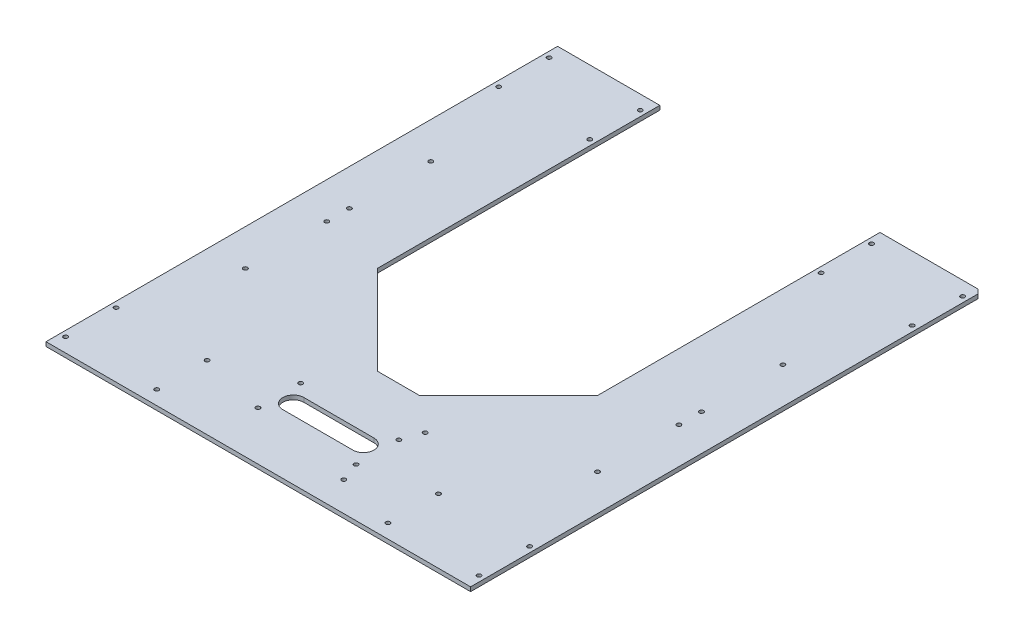
SolidWorks part; units mm, degrees
material "3.3315 (EN-AW 5005)"
ref_plane "Front Plane" through (0, 0, 0) normal (0, 0, 1) x (1, 0, 0)
ref_plane "Top Plane" through (0, 0, 0) normal (0, 1, 0) x (1, 0, 0)
ref_plane "Right Plane" through (0, 0, 0) normal (1, 0, 0) x (0, 0, -1)
sketch "Sketch1" plane through (0, 0, 0) normal (0, 1, 0) x (1, 0, 0)
  line L0 (0, 0) -> (0, -365)
  line L1 (0, -365) -> (302.93, -365)
  line L2 (302.93, -365) -> (302.93, 0)
  line L3 (302.93, 0) -> (230, 0)
  line L4 (230, 0) -> (230, -265)
  line L5 (230, -265) -> (72.93, -265)
  line L6 (72.93, -265) -> (72.93, 0)
  line L7 (72.93, 0) -> (0, 0)
  line L8 (72.93, -201.465) -> (136.465, -265)
  line L9 (166.465, -265) -> (230, -201.465)
  line L10 (151.465, -265) -> (151.465, -365) construction
  line L11 (126.465, -315) -> (176.465, -315) construction
  line L12 (126.465, -307.5) -> (176.465, -307.5)
  line L13 (126.465, -322.5) -> (176.465, -322.5)
  line L14 (0, -182.5) -> (72.93, -182.5) construction
  line L15 (116.465, -299.75) -> (186.465, -330.25) construction
  line L16 (191.465, -285.965) -> (191.465, -344.035) construction
  arc A0 (126.465, -307.5) -> (126.465, -322.5) centre (126.465, -315) ccw
  arc A1 (176.465, -322.5) -> (176.465, -307.5) centre (176.465, -315) ccw
  circle A2 centre (3.97, -10) radius 1.5
  circle A3 centre (3.97, -46.01) radius 1.5
  circle A4 centre (68.96, -10) radius 1.5
  circle A5 centre (68.96, -46.01) radius 1.5
  circle A6 centre (68.96, -318.99) radius 1.5
  circle A7 centre (68.96, -355) radius 1.5
  circle A8 centre (3.97, -318.99) radius 1.5
  circle A9 centre (3.97, -355) radius 1.5
  circle A10 centre (298.96, -355) radius 1.5
  circle A11 centre (298.96, -318.99) radius 1.5
  circle A12 centre (233.97, -355) radius 1.5
  circle A13 centre (233.97, -318.99) radius 1.5
  circle A14 centre (233.97, -46.01) radius 1.5
  circle A15 centre (233.97, -10) radius 1.5
  circle A16 centre (298.96, -46.01) radius 1.5
  circle A17 centre (298.96, -10) radius 1.5
  circle A18 centre (116.465, -330.25) radius 1.5
  circle A19 centre (116.465, -299.75) radius 1.5
  circle A20 centre (186.465, -299.75) radius 1.5
  circle A21 centre (186.465, -330.25) radius 1.5
  circle A22 centre (25.86, -116.36) radius 1.5
  circle A23 centre (25.86, -174.43) radius 1.5
  circle A24 centre (25.86, -190.57) radius 1.5
  circle A25 centre (25.86, -248.64) radius 1.5
  circle A26 centre (277.07, -248.64) radius 1.5
  circle A27 centre (277.07, -190.57) radius 1.5
  circle A28 centre (277.07, -174.43) radius 1.5
  circle A29 centre (277.07, -116.36) radius 1.5
  circle A30 centre (191.465, -344.035) radius 1.5
  circle A31 centre (191.465, -285.965) radius 1.5
  point P17 (151.465, -315)
  point P27 (151.465, -315)
  point P65 (151.465, -315)
  point P86 (191.465, -315)
  point P87 (0, 0)
  dimension "D12" = 3
  dimension "D18" = 3
  dimension "D20" = 3
  dimension "D28" = 3
  dimension "D1" = 365
  dimension "D2" = 72.93
  dimension "D3" = 72.93
  dimension "D4" = 100
  dimension "D5" = 302.93
  dimension "D6" = 63.535
  dimension "D7" = 63.535
  dimension "D8" = 63.535
  dimension "D9" = 63.535
  dimension "D10" = 15
  dimension "D11" = 50
  dimension "D13" = 3.97
  dimension "D14" = 3.97
  dimension "D15" = 36.01
  dimension "D16" = 10
  dimension "D17" = 30.5
  dimension "D19" = 70
  dimension "D21" = 25.86
  dimension "D22" = 116.36
  dimension "D23" = 58.07
  dimension "D24" = 58.07
  dimension "D25" = 58.07
  dimension "D26" = 116.36
  dimension "D27" = 40
extrude "Boss-Extrude1" add sketch "Sketch1" along normal blind 3 contours L8 L6 L5 | L6 L7 L0 L1 L2 L3 L4 L5 | L9 L5 L4 region at (36.465, 0, 4.7433) region at (94.1083, 0, 243.8217) region at (208.8217, 0, 243.8217)
chamfer "Chamfer1" distance 3 angle 45 1 edges at (302.93, 1.5, 0)
